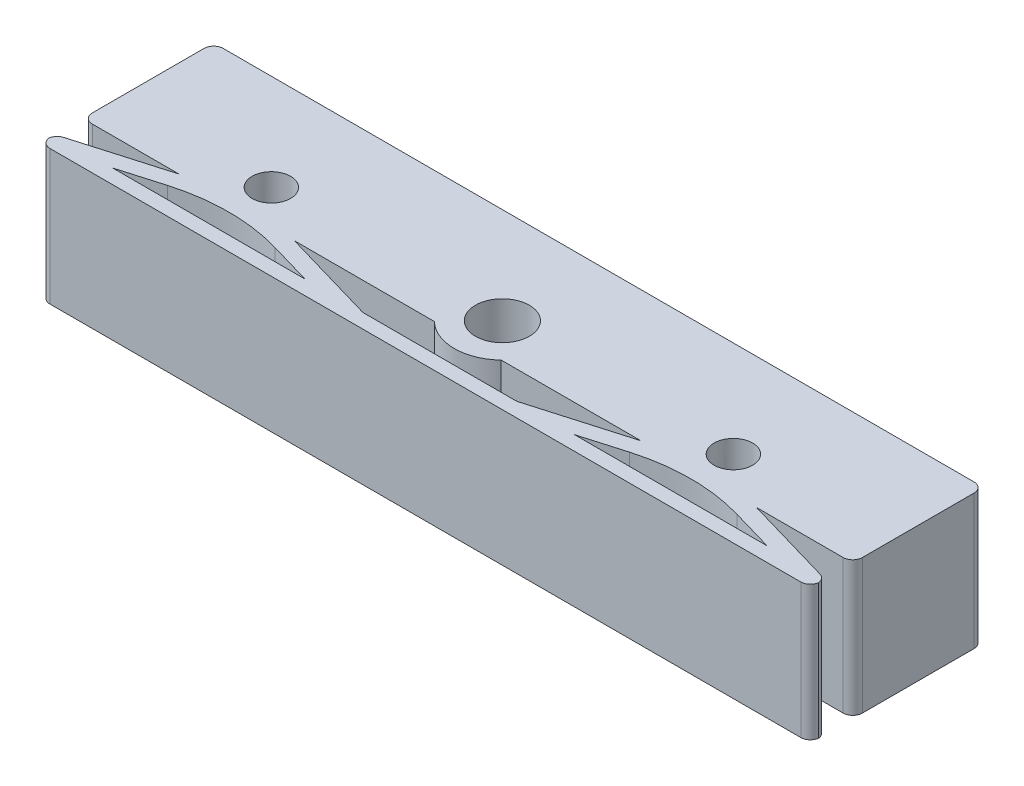
SolidWorks part; units mm, degrees
ref_plane "Front Plane" through (0, 0, 0) normal (0, 0, 1) x (1, 0, 0)
ref_plane "Top Plane" through (0, 0, 0) normal (0, 1, 0) x (1, 0, 0)
ref_plane "Right Plane" through (0, 0, 0) normal (1, 0, 0) x (0, 0, -1)
sketch "Sketch1" plane through (0, 0, 0) normal (0, 1, 0) x (1, 0, 0)
  line L0 (0, 0) -> (0, 9)
  line L1 (0, 9) -> (40, 9)
  line L2 (40, 9) -> (40, 0)
  line L3 (0, 0) -> (40, 0)
  dimension "D1" = 40
  dimension "D2" = 9
extrude "Boss-Extrude1" add sketch "Sketch1" along normal blind 7
sketch "Sketch2" plane through (0, 7, 0) normal (0, 1, 0) x (1, 0, 0)
  line L0 (0, 9) -> (8, 9)
  line L1 (40, 9) -> (0, 9) construction
  line L2 (8, 9) -> (8, 4)
  line L3 (8, 4) -> (32, 4)
  line L4 (0, 0) -> (0, 2.2) construction
  line L5 (0, 9) -> (0, 0) construction
  line L6 (0, 2.2) -> (19.4811, 2.2) construction
  line L7 (0, 2.2) -> (5, 2.2)
  line L8 (5, 2.2) -> (8, 2.2)
  line L9 (0, 0) -> (0, 0.75)
  line L10 (5, 2.2) -> (0, 0.75)
  line L11 (0, 0.75) -> (0, 2.2)
  line L12 (0, 0.75) -> (3, 0.75)
  line L13 (3, 0.75) -> (8, 2.2)
  line L14 (0, 0.75) -> (12.9505, 0.75) construction
  line L15 (16, 0.75) -> (13, 0.75)
  line L17 (8, 2.2) -> (11, 2.2)
  line L18 (8, 2.2) -> (13, 0.75)
  line L19 (11, 2.2) -> (16, 0.75)
  line L20 (24, 0.75) -> (27, 0.75)
  line L22 (40, 2.2) -> (35, 2.2)
  line L23 (40, 0) -> (40, 9) construction
  line L24 (35, 2.2) -> (32, 2.2)
  line L25 (32, 2.2) -> (29, 2.2)
  line L26 (24, 0.75) -> (29, 2.2)
  line L27 (27, 0.75) -> (32, 2.2)
  line L28 (40, 0.75) -> (37, 0.75)
  line L29 (32, 2.2) -> (37, 0.75)
  line L30 (35, 2.2) -> (40, 0.75)
  line L31 (3, 0.75) -> (13, 0.75)
  line L32 (11, 2.2) -> (16, 2.2)
  line L33 (16, 2.2) -> (16, 0)
  line L34 (0, 0) -> (40, 0) construction
  line L35 (24, 2.2) -> (29, 2.2)
  line L36 (27, 0.75) -> (37, 0.75)
  line L37 (40, 0.75) -> (40, 2.2)
  line L38 (16, 0) -> (24, 0)
  line L39 (24, 0) -> (24, 2.2)
  line L40 (16, 2.2) -> (24, 2.2)
  line L41 (16, 0.75) -> (24, 0.75)
  circle A0 centre (8, 4) radius 1
  circle A1 centre (32, 4) radius 1
  circle A2 centre (20, 4) radius 1.4
  circle A3 centre (20, 4) radius 2.5
  dimension "D2" = 2
  dimension "D4" = 2
  dimension "D20" = 2.8
  dimension "D21" = 5
  dimension "D1" = 8
  dimension "D3" = 24
  dimension "D5" = 5
  dimension "D6" = 2.2
  dimension "D7" = 0.75
  dimension "D8" = 5
  dimension "D9" = 3
  dimension "D10" = 3
  dimension "D11" = 3
  dimension "D12" = 3
  dimension "D13" = 3
  dimension "D14" = 5
  dimension "D15" = 3
  dimension "D16" = 3
  dimension "D17" = 3
  dimension "D18" = 5
  dimension "D19" = 5
extrude "Cut-Extrude1" cut sketch "Sketch2" along normal blind 5 and the other way blind 10
fillet "Fillet1" radius 10 2 edges at (32, 3.5, -2.2) (8, 3.5, -2.2)
fillet "Fillet2" radius 0.5 10 edges at (24, 3.5, -0.75) (16, 3.5, -0.75) (0, 3.5, -2.2) (0, 3.5, -9) (40, 3.5, -9) (40, 3.5, -2.2) (40, 3.5, -0.75) (40, 3.5, 0) (0, 3.5, 0) (0, 3.5, -0.75)
sketch "Sketch3" plane through (0, 0, -9) normal (0, 0, -1) x (-1, 0, 0)
  line L0 (-40, 7) -> (-32, 7) construction
  line L1 (-39.5, 7) -> (-0.5, 7) construction
  line L2 (-32, 7) -> (-32, 3.5) construction
  line L3 (-32, 3.5) -> (-8, 3.5) construction
  line L4 (-8, 3.5) -> (-8, 7) construction
  line L5 (-8, 7) -> (0, 7) construction
  circle A0 centre (-32, 3.5) radius 1.75
  circle A1 centre (-8, 3.5) radius 1.75
  dimension "D4" = 3.5
  dimension "D5" = 3.5
  dimension "D1" = 8
  dimension "D2" = 8
  dimension "D3" = 3.5
extrude "Cut-Extrude6" cut sketch "Sketch3" against normal blind 3.8
sketch "Sketch4" plane through (0, 0, -5.2) normal (0, 0, -1) x (-1, 0, 0)
  line L0 (-32, 3.5) -> (-33.75, 3.5) construction
  line L2 (-32, 3.5) -> (-30.25, 3.5) construction
  line L4 (-30.25, 3.75) -> (-33.75, 3.75)
  line L6 (-33.75, 3.25) -> (-30.25, 3.25)
  line L7 (-30.25, 3.25) -> (-30.25, 3.75)
  line L8 (-33.75, 3.25) -> (-33.75, 3.75)
  line L9 (-9.75, 3.5) -> (-6.25, 3.5) construction
  line L10 (-6.25, 3.25) -> (-6.25, 3.75)
  line L11 (-9.75, 3.25) -> (-9.75, 3.75)
  line L12 (-9.75, 3.75) -> (-6.25, 3.75)
  line L13 (-6.25, 3.25) -> (-9.75, 3.25)
  circle A0 centre (-32, 3.5) radius 1.75 construction
  circle A1 centre (-32, 3.5) radius 1.75 construction
  circle A2 centre (-8, 3.5) radius 1.75 construction
  circle A3 centre (-8, 3.5) radius 1.75 construction
  point P14 (-30.25, 3.5)
  point P15 (-33.75, 3.5)
  point P20 (-8, 3.5)
  point P22 (-6.25, 3.5)
  point P23 (-33.25, 3.75)
  point P26 (-9.75, 3.5)
  dimension "D1" = 0.5
  dimension "D2" = 0.5
  dimension "D3" = 3.5
  dimension "D4" = 0.5
extrude "Cut-Extrude7" cut sketch "Sketch4" against normal blind 2.5
